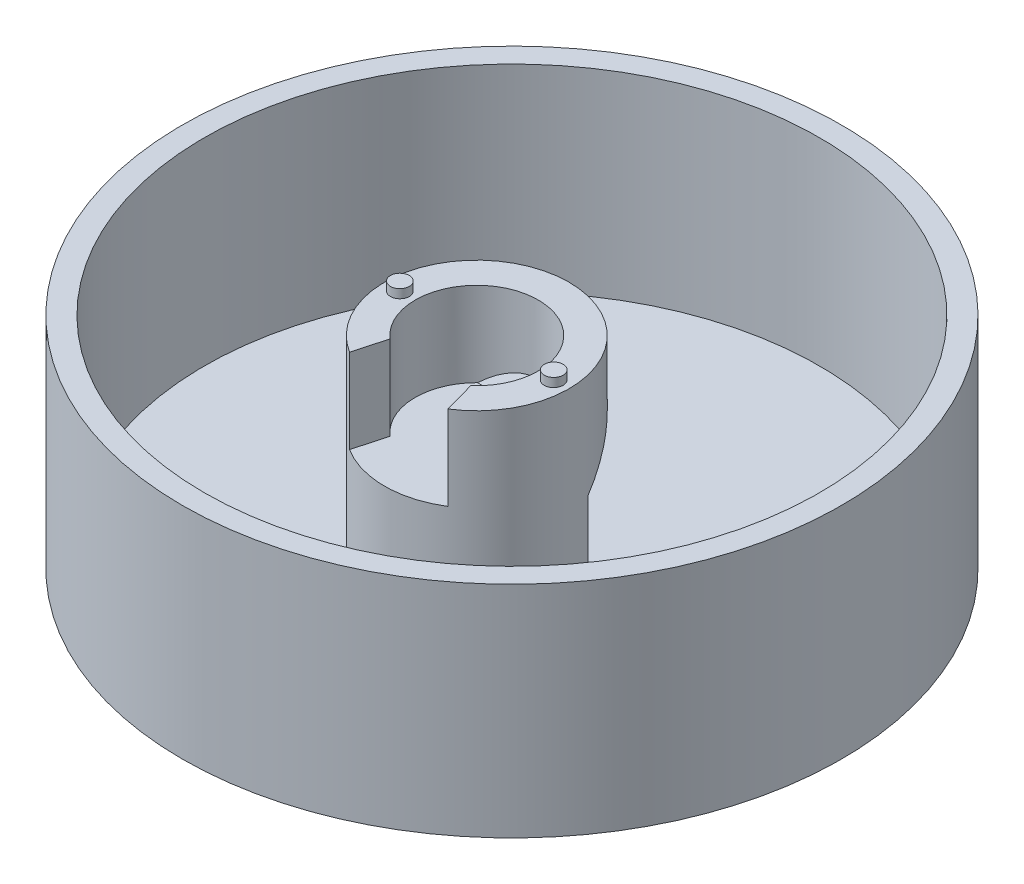
SolidWorks part; units mm, degrees
ref_plane "Front Plane" through (0, 0, 0) normal (0, 0, 1) x (1, 0, 0)
ref_plane "Top Plane" through (0, 0, 0) normal (0, 1, 0) x (1, 0, 0)
ref_plane "Right Plane" through (0, 0, 0) normal (1, 0, 0) x (0, 0, -1)
sketch "Sketch1" plane through (0, 0, 0) normal (0, 1, 0) x (1, 0, 0)
  circle A0 centre (0, 0) radius 75
  dimension "D1" = 150
extrude "Boss-Extrude1" add sketch "Sketch1" along normal blind 50
shell "Shell1" thickness 5 removed face at (0, 50, 75)
sketch "Sketch2" plane through (0, 5, 0) normal (0, 1, 0) x (1, 0, 0)
  circle A0 centre (0, -8) radius 21
  point P3 (0, 0)
  point P4 (0, -12.7391)
  dimension "D1" = 42
  dimension "D2" = 8
extrude "Boss-Extrude2" add sketch "Sketch2" along normal up to surface (45 mm away) up to face at (0, 50, 70)
sketch "Sketch3" plane through (0, 50, 0) normal (0, 1, 0) x (1, 0, 0)
  line L0 (0, 24.8098) -> (0, -28.2587) construction
  line L1 (9.2, -18.5527) -> (-9.2, -18.5527) construction
  line L2 (-9.2, -18.5527) -> (-11.1933, -25.7683)
  line L3 (9.2, -18.5527) -> (11.1933, -25.7683)
  line L4 (-17.5, -8) -> (17.5, -8) construction
  circle A0 centre (0, -8) radius 14
  circle A1 centre (0, -8) radius 21
  circle A2 centre (-17.5, -8) radius 2.15
  circle A3 centre (17.5, -8) radius 2.15
  point P9 (-17.5, -8)
  point P10 (17.5, -8)
  point P14 (0, 24.8098)
  point P17 (0, 0)
  point P18 (0, -8)
  circle M1 centre (0, -8) radius 21
  dimension "D1" = 28
  dimension "D2" = 42
  dimension "D4" = 17.5
  dimension "D5" = 4.3
  dimension "D3" = 18.4
  dimension "D6" = 8
extrude "Cut-Extrude1" cut sketch "Sketch3" against normal blind 19.2 contours A0 L2 L3 M1 | A0 region at (0, 50, 24.4794)
extrude "Boss-Extrude3" add sketch "Sketch3<3>" along normal blind 2 contours A2 | A3 region at (-17.5, 50, 8) region at (17.5, 50, 8)
sketch "Sketch3<3>" plane through (0, 50, 0) normal (0, 1, 0) x (1, 0, 0) same geometry as "Sketch3"
sketch "Sketch4" plane through (0, 5, 0) normal (0, 1, 0) x (1, 0, 0)
  line L1 (57.3258, 35.7402) -> (4.3258, 35.7402)
  line L2 (57.3258, 35.7402) -> (57.3258, -34.2598)
  line L3 (57.3258, -34.2598) -> (4.3258, -34.2598)
  line L4 (4.3258, 35.7402) -> (4.3258, -34.2598)
  point P4 (57.3258, 35.7402)
  dimension "D1" = 70
  dimension "D2" = 53
extrude "Cut-Extrude2" [suppressed] cut sketch "Sketch4" along normal blind 17 contours L2 L3 L4 L1
ref_plane "Plane1" through (0, 50, -13) normal (-1, 0, 0) x (0, 0, 1)
sketch "Sketch6" plane through (0, 50, -13) normal (-1, 0, 0) x (0, 0, 1)
  line L0 (-3.4087, -45) -> (16.1821, -45)
  line L1 (83, -45) -> (-57, -45) construction
  line L2 (42, -45) -> (0, -45) construction
  line L3 (16.1821, -45) -> (16.1821, -23.8565)
  line L4 (16.1821, -23.8565) -> (0, -9.2577)
  line L5 (0, -9.2577) -> (-3.4087, -9.2577)
  line L6 (-3.4087, -9.2577) -> (-3.4087, -45)
extrude "Cut-Extrude3" cut sketch "Sketch6" against normal blind 27 and the other way blind 32
